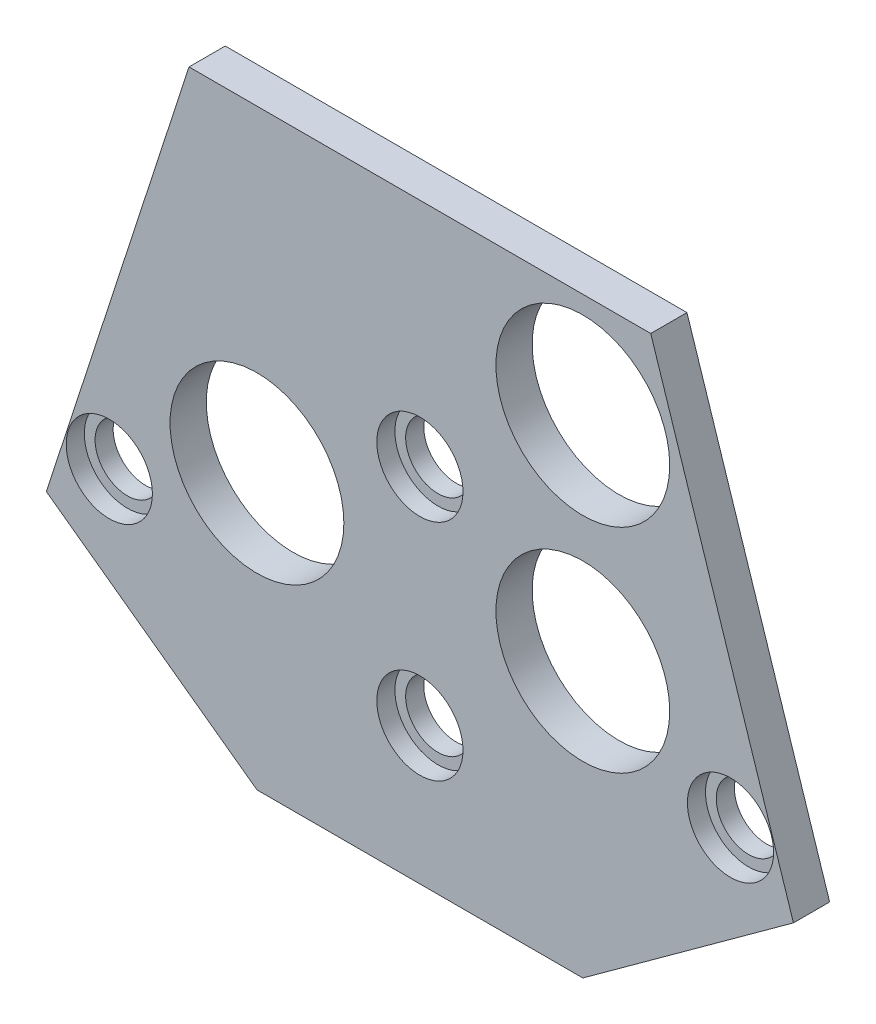
SolidWorks part; units mm, degrees
ref_plane "Front Plane" through (0, 0, 0) normal (0, 0, 1) x (1, 0, 0)
ref_plane "Top Plane" through (0, 0, 0) normal (0, 1, 0) x (1, 0, 0)
ref_plane "Right Plane" through (0, 0, 0) normal (1, 0, 0) x (0, 0, -1)
sketch "Sketch1" plane through (0, 0, 0) normal (0, 0, 1) x (1, 0, 0)
  line L1 (-304.8, 230.1875) -> (304.8, 230.1875)
  line L2 (-304.8, 230.1875) -> (-304.8, -230.1875)
  line L3 (-304.8, -230.1875) -> (304.8, -230.1875)
  line L4 (304.8, 230.1875) -> (304.8, -230.1875)
  line L5 (-304.8, 230.1875) -> (304.8, -230.1875) construction
  line L6 (-304.8, -230.1875) -> (304.8, 230.1875) construction
  point P0 (0, 0)
  dimension "D1" = 460.375
  dimension "D2" = 609.6
extrude "Boss-Extrude1" [suppressed] add sketch "Sketch1" along normal blind 5.334
sketch "Sketch2" plane through (0, 0, 0) normal (0, 0, 1) x (1, 0, 0)
  line L0 (-37.5261, 4.1449) -> (-10.4739, 36.2724) construction
  line L1 (-24, 20.2087) -> (24, 20.2087) construction
  line L2 (-24, 20.2087) -> (-24, -20.2087) construction
  line L3 (-24, -20.2087) -> (24, -20.2087)
  line L4 (24, 20.2087) -> (24, -20.2087) construction
  line L5 (-24, 20.2087) -> (24, -20.2087) construction
  line L6 (-24, -20.2087) -> (24, 20.2087) construction
  line L7 (0, -37.6457) -> (55.0228, 2.3307)
  line L8 (55.0228, 2.3307) -> (34.0059, 67.0138)
  line L9 (34.0059, 67.0138) -> (-34.0059, 67.0138)
  line L10 (-34.0059, 67.0138) -> (-55.0228, 2.3307)
  line L11 (-55.0228, 2.3307) -> (0, -37.6457)
  line L12 (-13.5261, -16.0637) -> (-47.1372, 12.2377) construction
  line L13 (13.5261, 16.0637) -> (-25.038, 48.5358) construction
  line L14 (24, 20.2087) -> (24, 82.9587) construction
  circle A0 centre (0, 0) radius 4.7625
  circle A1 centre (0, 0) radius 21 construction
  circle A2 centre (24, 20.2087) radius 12.8
  circle A3 centre (-24, 20.2087) radius 12.8
  circle A4 centre (0, 20.2087) radius 46.8052 construction
  circle A5 centre (24, 51.5837) radius 12.8
  point P0 (0, 0)
  point P21 (-24, 20.2087)
  dimension "D2" = 9.525
  dimension "D3" = 42
  dimension "D5" = 25.6
  dimension "D1" = 31.375
  dimension "D4" = 48
extrude "Boss-Extrude2" add sketch "Sketch2" along normal blind 5.334 contours L10 L11 L3 L7 L8 L9 A3 A2 A0 region at (-2.0852, 20.9914, 0)
sketch "Sketch3" plane through (0, 0, 5.334) normal (0, 0, 1) x (1, 0, 0)
  line L0 (55.0228, 2.3307) -> (36.4806, 17.367) construction
  line L1 (-55.0228, 2.3307) -> (-36.4806, 17.367) construction
  line L2 (-24, 33.0087) -> (24, 33.0087) construction
  circle A0 centre (0, 0) radius 6.35
  circle A1 centre (24, 20.2087) radius 12.8 construction
  circle A2 centre (-24, 20.2087) radius 12.8 construction
  circle A3 centre (45.7517, 9.8488) radius 6.35
  circle A4 centre (0, 33.0087) radius 6.35
  circle A5 centre (-45.7517, 9.8488) radius 6.35
  circle A6 centre (0, 0) radius 4.7625
  circle A7 centre (45.7517, 9.8488) radius 4.7625
  circle A8 centre (0, 33.0087) radius 4.7625
  circle A9 centre (-45.7517, 9.8488) radius 4.7625
  dimension "D1" = 12.7
extrude "Cut-Extrude3" cut sketch "Sketch3" against normal blind 2.667
extrude "Cut-Extrude4" cut sketch "Sketch3<2>" against normal through all contours A9 | A8 | A7 region at (45.7517, 9.8488, 5.334) region at (0, 33.0087, 5.334) region at (-45.7517, 9.8488, 5.334)
sketch "Sketch3<2>" plane through (0, 0, 5.334) normal (0, 0, 1) x (1, 0, 0) same geometry as "Sketch3"
